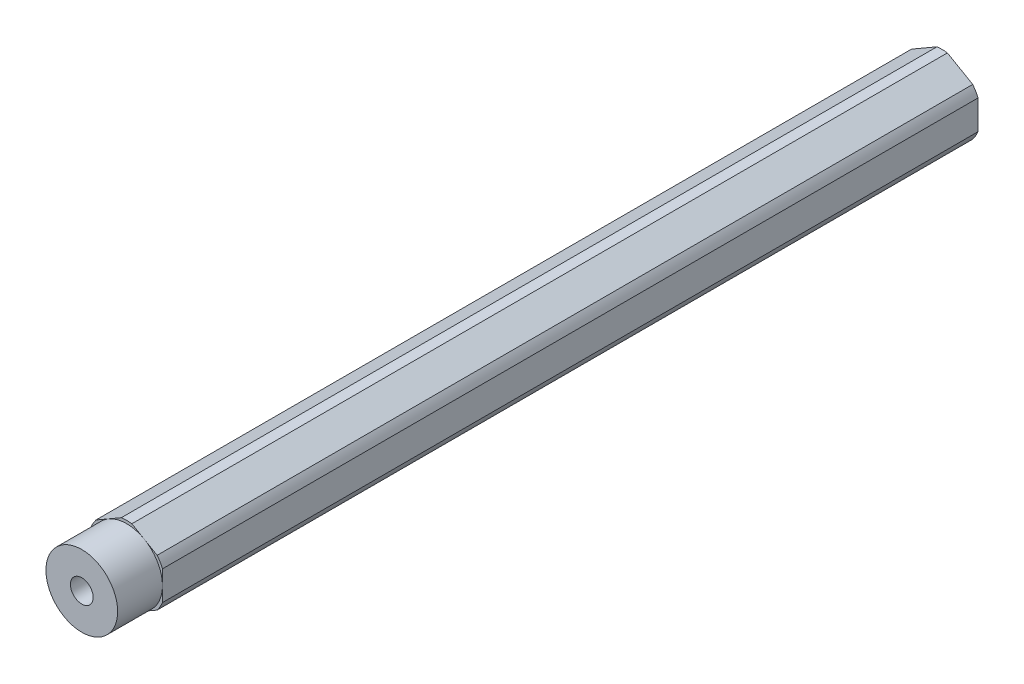
SolidWorks part; units mm, degrees
ref_plane "Front Plane" through (0, 0, 0) normal (0, 0, 1) x (1, 0, 0)
ref_plane "Top Plane" through (0, 0, 0) normal (0, 1, 0) x (1, 0, 0)
ref_plane "Right Plane" through (0, 0, 0) normal (1, 0, 0) x (0, 0, -1)
sketch "Sketch1" plane through (0, 0, 0) normal (0, 0, 1) x (1, 0, 0)
  line L1 (0, 7.3323) -> (-6.35, 3.6662)
  line L2 (-6.35, 3.6662) -> (-6.35, -3.6662)
  line L3 (-6.35, -3.6662) -> (0, -7.3323)
  line L4 (0, -7.3323) -> (6.35, -3.6662)
  line L5 (6.35, -3.6662) -> (6.35, 3.6662)
  line L6 (6.35, 3.6662) -> (0, 7.3323)
  circle A0 centre (0, 0) radius 6.35 construction
  circle A1 centre (0, 0) radius 6.858
  circle A2 centre (0, 0) radius 2.0193
  dimension "D1" = 12.7
  dimension "D2" = 13.716
  dimension "D3" = 4.0386
extrude "Boss-Extrude1" add sketch "Sketch1" along normal mid plane 144.4625 contours L5 A1 L6 L1 L2 L3 L4 region at (0, 6.6711, 0)
sketch "Sketch2" plane through (0, 0, 72.2313) normal (0, 0, 1) x (1, 0, 0)
  circle A0 centre (0, 0) radius 6.35
  circle A1 centre (0, 0) radius 2.0193
  dimension "D1" = 12.7
  dimension "D2" = 4.0386
extrude "Boss-Extrude2" add sketch "Sketch2" along normal blind 7.9375
